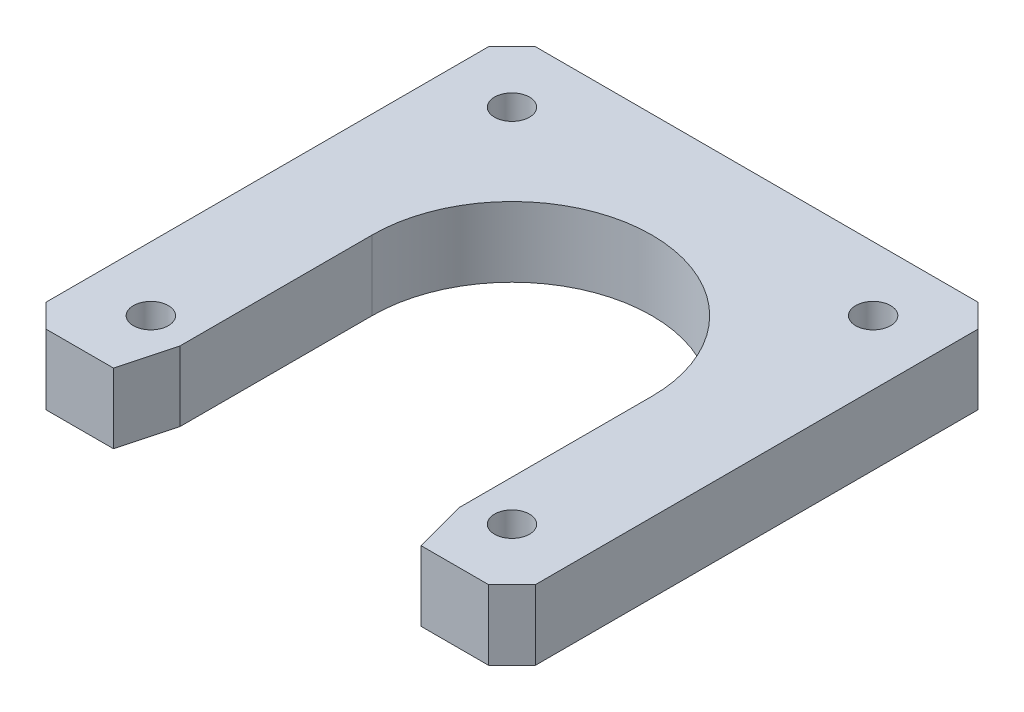
SolidWorks part; units mm, degrees
ref_plane "Front Plane" through (0, 0, 0) normal (0, 0, 1) x (1, 0, 0)
ref_plane "Top Plane" through (0, 0, 0) normal (0, 1, 0) x (1, 0, 0)
ref_plane "Right Plane" through (0, 0, 0) normal (1, 0, 0) x (0, 0, -1)
sketch "Sketch1" plane through (0, 0, 0) normal (0, 1, 0) x (1, 0, 0)
  line L1 (-21, -21) -> (21, -21)
  line L2 (-21, -21) -> (-21, 21)
  line L3 (-21, 21) -> (21, 21)
  line L4 (21, -21) -> (21, 21)
  line L5 (-21, -21) -> (21, 21) construction
  line L6 (-21, 21) -> (21, -21) construction
  line L7 (-15.5, 15.5) -> (15.5, 15.5) construction
  line L8 (-15.5, 15.5) -> (-15.5, -15.5) construction
  line L9 (-15.5, -15.5) -> (15.5, -15.5) construction
  line L10 (15.5, 15.5) -> (15.5, -15.5) construction
  circle A0 centre (0, 0) radius 12
  circle A1 centre (-15.5, 15.5) radius 1.5
  circle A2 centre (15.5, 15.5) radius 1.5
  circle A3 centre (15.5, -15.5) radius 1.5
  circle A4 centre (-15.5, -15.5) radius 1.5
  point P0 (0, 0)
  dimension "D2" = 24
  dimension "D3" = 3
  dimension "D1" = 42
  dimension "D4" = 31
extrude "Boss-Extrude1" add sketch "Sketch1" along normal blind 6
chamfer "Chamfer1" distance 2 angle 45 4 edges at (-21, 3, -21) (21, 3, -21) (21, 3, 21) (-21, 3, 21)
sketch "Sketch2" plane through (0, 6, 0) normal (0, 1, 0) x (1, 0, 0)
  line L0 (-12, 0) -> (-12, -21)
  line L1 (-19, -21) -> (19, -21) construction
  line L2 (-12, -21) -> (12, -21)
  line L3 (12, -21) -> (12, 0)
  line L4 (12, 0) -> (-12, 0)
  circle A0 centre (0, 0) radius 12 construction
extrude "Cut-Extrude1" cut sketch "Sketch2" against normal through all
chamfer "Chamfer2" distance 4.5 angle 15 2 edges at (12, 3, 21) (-12, 3, 21) first distance on face at (12, 3, 10.5) first distance on face at (-12, 3, 10.5)
equation "\"M3_d\"= \"M3_d_laser@troublemaker.Assembly\""
equation "\"housing_t\"= \"housing_t_glob@troublemaker.Assembly\""
equation "\"D3@Sketch1\"=\"M3_d\""
equation "\"D1@Boss-Extrude1\"=\"housing_t\""
